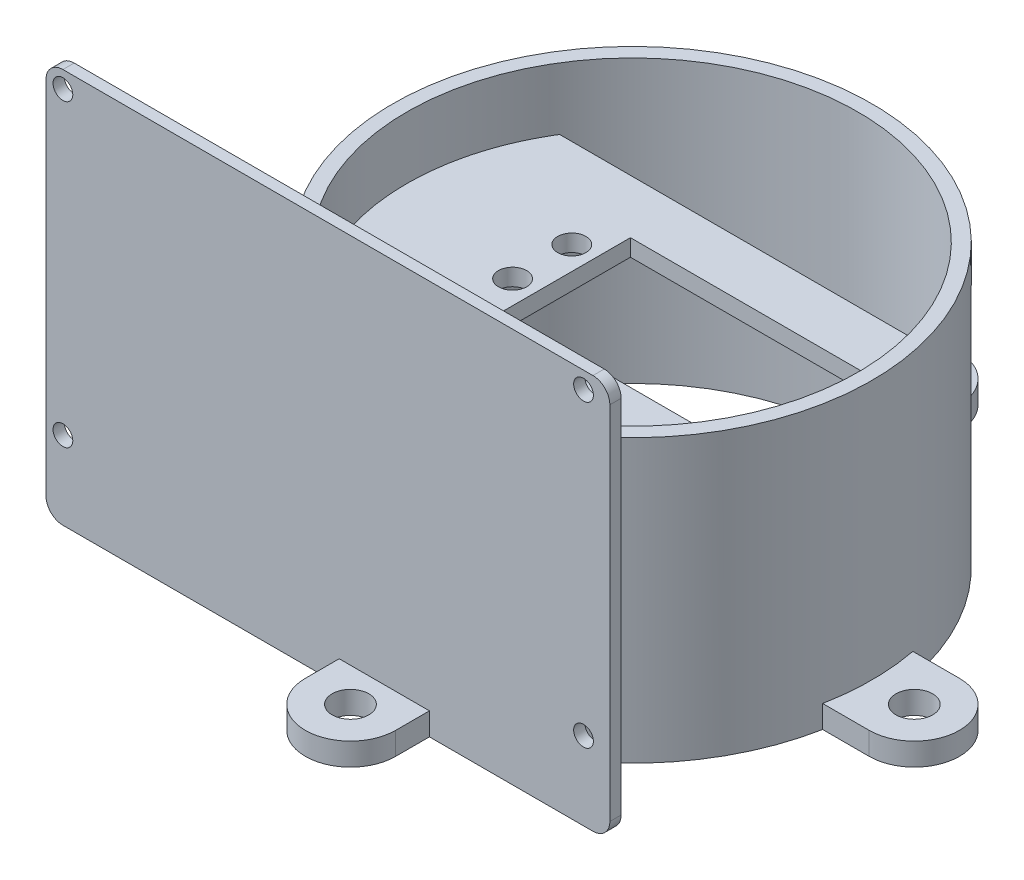
SolidWorks part; units mm, degrees
ref_plane "Front Plane" through (0, 0, 0) normal (0, 0, 1) x (1, 0, 0)
ref_plane "Top Plane" through (0, 0, 0) normal (0, 1, 0) x (1, 0, 0)
ref_plane "Right Plane" through (0, 0, 0) normal (1, 0, 0) x (0, 0, -1)
sketch "Sketch1" plane through (0, 0, 0) normal (0, 1, 0) x (1, 0, 0)
  circle A0 centre (0, 0) radius 40
  circle A1 centre (0, 0) radius 42.5
  dimension "D1" = 80
  dimension "D2" = 85
extrude "Boss-Extrude1" add sketch "Sketch1" along normal blind 50
sketch "Sketch2" plane through (0, 0, 0) normal (0, -1, 0) x (1, 0, 0)
  line L0 (42.5, 0) -> (50.0003, 0) construction
  line L1 (41.7403, 8) -> (50.0003, 8)
  line L2 (41.7403, -8) -> (50.0003, -8)
  circle A0 centre (0, 0) radius 42.5 construction
  circle A1 centre (50.0003, 0) radius 3.25
  arc A2 (50.0003, -8) -> (50.0003, 8) centre (50.0003, 0) ccw
  circle M3 centre (0, 0) radius 42.5
  dimension "D2" = 6.5
  dimension "D4" = 16
  dimension "D1" = 8.26
  dimension "D3" = 8
extrude "Boss-Extrude2" add sketch "Sketch2" against normal blind 4 contours L2 A2 L1 A1 M3 region at (45.8703, 0, 7.7719)
pattern_circular "CirPattern1" count 4 over 360 about axis through (0, 0, 0) along (0, 1, 0) of "Boss-Extrude2"
ref_plane "Plane1" through (0, 36, 0) normal (0, 1, 0) x (1, 0, 0)
sketch "Sketch4" plane through (0, 36, 0) normal (0, 1, 0) x (1, 0, 0)
  line L5 (34, -21.0713) -> (-34, -21.0713)
  line L7 (34, 21.0713) -> (-34, 21.0713)
  line L9 (34, -21.0713) -> (-34, 21.0713) construction
  line L10 (34, 21.0713) -> (-34, -21.0713) construction
  circle A3 centre (0, 0) radius 40 construction
  arc A4 (-34, 21.0713) -> (-34, -21.0713) centre (0, 0) ccw
  arc A5 (34, -21.0713) -> (34, 21.0713) centre (0, 0) ccw
  point P0 (0, 0)
  dimension "D1" = 68
extrude "Boss-Extrude3" add sketch "Sketch4" along normal blind 3 separate body
sketch "Sketch3" plane through (0, 39, 0) normal (0, 1, 0) x (1, 0, 0)
  line L0 (-15.9997, 5.25) -> (34.3003, 5.25) construction
  line L1 (-15.9997, 5.25) -> (-15.9997, -5.25) construction
  line L2 (-15.9997, -5.25) -> (34.3003, -5.25) construction
  line L3 (34.3003, 5.25) -> (34.3003, -5.25) construction
  line L4 (-15.9997, 5.25) -> (34.3003, -5.25) construction
  line L5 (34.3003, -5.25) -> (34.3003, 5.25) construction
  line L6 (34.3003, 5.25) -> (-15.9997, -5.25) construction
  line L7 (30.1503, -11.5) -> (-11.8497, -11.5)
  line L8 (30.1503, -11.5) -> (30.1503, 11.5)
  line L9 (30.1503, 11.5) -> (-11.8497, 11.5)
  line L10 (-11.8497, -11.5) -> (-11.8497, 11.5)
  line L11 (30.1503, -11.5) -> (-11.8497, 11.5) construction
  line L12 (30.1503, 11.5) -> (-11.8497, -11.5) construction
  line L13 (9.1503, 0) -> (50.0003, 0) construction
  circle A0 centre (34.3003, 5.25) radius 2.5
  circle A1 centre (34.3003, -5.25) radius 2.5
  circle A2 centre (-15.9997, -5.25) radius 2.5
  circle A3 centre (-15.9997, 5.25) radius 2.5
  circle A4 centre (9.1503, 0) radius 12.5 construction
  point P14 (0, 0)
  dimension "D1" = 5
  dimension "D4" = 25
  dimension "D2" = 10.5
  dimension "D3" = 50.3
  dimension "D5" = 42
  dimension "D6" = 23
  dimension "D7" = 40.85
extrude "Cut-Extrude1" cut sketch "Sketch3" against normal up to next (3 mm away)
sketch "Sketch5" plane through (0, 0, 0) normal (0, 0, 1) x (1, 0, 0)
  line L0 (0, 0) -> (0, 36) construction
  line L1 (-60, 70) -> (40, 70)
  line L2 (-60, 70) -> (-60, 0)
  line L3 (-60, 0) -> (40, 0)
  line L4 (40, 70) -> (40, 0)
  line L5 (46.75, 36) -> (-46.75, 36) construction
  line L6 (-10, 0) -> (-10, 70) construction
  line L7 (8, 0) -> (41.7403, 0) construction
  circle A0 centre (-57, 67) radius 1.75
  circle A1 centre (35.33, 67) radius 1.75
  circle A2 centre (-57, 13.85) radius 1.75
  circle A3 centre (35.33, 13.85) radius 1.75
  point P7 (0, 0)
  point P20 (0, 0)
  dimension "D3" = 3.5
  dimension "D4" = 92.33
  dimension "D5" = 3
  dimension "D6" = 3
  dimension "D8" = 53.15
  dimension "D1" = 100
  dimension "D2" = 70
  dimension "D9" = 10
  dimension "D7" = 2
extrude "Boss-Extrude4" add sketch "Sketch5" along normal blind 2 from offset 42
fillet "Fillet1" radius 3 4 edges at (40, 70, 43) (-60, 70, 43) (40, 0, 43) (-60, 0, 43)
